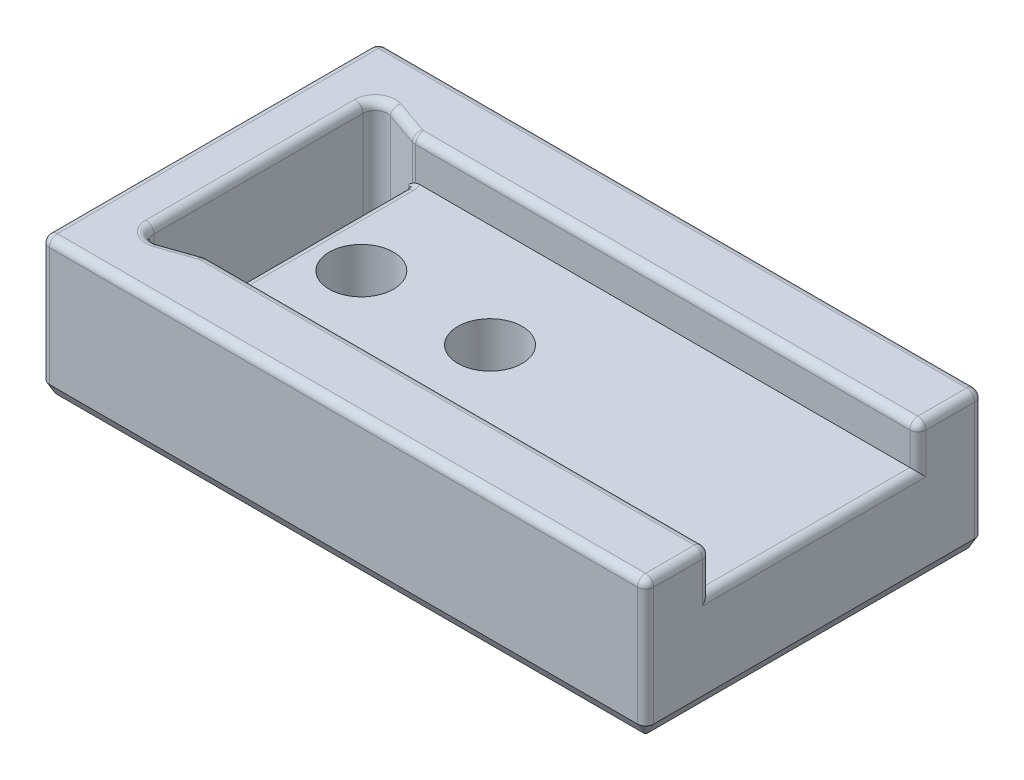
SolidWorks part; units mm, degrees
ref_plane "Front Plane" through (0, 0, 0) normal (0, 0, 1) x (1, 0, 0)
ref_plane "Top Plane" through (0, 0, 0) normal (0, 1, 0) x (1, 0, 0)
ref_plane "Right Plane" through (0, 0, 0) normal (1, 0, 0) x (0, 0, -1)
ref_axis "Axis X" through (-88.99, 0, 0) along (1, 0, 0)
ref_axis "Axis Y" through (0, 55, 0) along (0, -1, 0)
ref_axis "Axis Z" through (0, 0, -88.99) along (0, 0, 1)
sketch "Sketch1" plane through (0, 0, 0) normal (0, 1, 0) x (1, 0, 0)
  line L0 (3, 7.5) -> (3, -7.5)
  line L1 (0, -10.4) -> (37.2875, -10.4)
  line L2 (0, -10.4) -> (0, 10.4)
  line L3 (0, 10.4) -> (37.2875, 10.4)
  line L4 (37.2875, -10.4) -> (37.2875, 10.4)
  line L5 (6.175, -6.4) -> (37.2875, -6.4)
  line L6 (6.175, 6.4) -> (37.2875, 6.4)
  line L7 (-4.675, 0) -> (4.675, 0) construction
  line L8 (6.175, 6.4) -> (6.175, -6.4)
  line L9 (3, 7.5) -> (6.175, 6.4)
  line L10 (3, -7.5) -> (6.175, -6.4)
  point P4 (0, 0)
  point P8 (9.35, 0)
  point P11 (17.2875, 0)
  point P16 (3, 0)
  dimension "D1" = 12.8
  dimension "D2" = 20
  dimension "D3" = 7.9375
  dimension "D4" = 6.35
  dimension "D5" = 4
  dimension "D6" = 3
  dimension "D7" = 3.175
  dimension "D8" = 15
extrude "Boss-Extrude1" add sketch "Sketch1" along normal blind 2.5 contours L0 L6 L4 L3 L2 L1 L5 region at (2.573, 0, 0)
extrude "Boss-Extrude2" add sketch "Sketch1<3>" against normal blind 6 contours L6 L8 L5 L4 | L0 L6 L4 L3 L2 L1 L5 region at (2.573, 0, 0) region at (21.7313, 0, 0)
sketch "Sketch1<3>" plane through (0, 0, 0) normal (0, 1, 0) x (1, 0, 0) same geometry as "Sketch1"
fillet "Fillet1" radius 0.75 4 edges at (3, -1.75, 7.5) (6.175, -3, 6.4) (6.175, -3, -6.4) (3, -1.75, -7.5)
fillet "Fillet2" radius 0.75 2 edges at (6.175, 1.25, 6.4) (6.175, 1.25, -6.4)
fillet "Fillet3" radius 0.5 24 edges at (37.2875, 2.5, 8.4) (18.6438, 2.5, 10.4) (0, 2.5, 0) (18.6438, 2.5, -10.4) (37.2875, 2.5, -8.4) (21.7944, 2.5, -6.4) (6.1768, 2.5, -6.4104) (5.0256, 2.5, -6.7982) (3.3151, 2.5, -7.0574) (3, 2.5, 0) (3.3151, 2.5, 7.0574) (5.0256, 2.5, 6.7982) (6.1768, 2.5, 6.4104) (21.7944, 2.5, 6.4) (0, -1.75, -10.4) (0, -1.75, 10.4) (37.2875, -1.75, -10.4) (37.2875, -1.75, 10.4) (37.2875, 1.25, 6.4) (37.2875, 1.25, -6.4) (6.036, 0, -6.3011) (6.036, 0, 6.3011) (6.175, 0, 0) (37.2875, 0, 0)
hole_wizard "5/32 (0.15625) Diameter Hole1" positions "Sketch2" profile "Sketch3" hole size "5/32" standard "ANSI Inch" end condition up to next
sketch "Sketch2" plane through (0, 0, 0) normal (0, 1, 0) x (1, 0, 0)
  point P0 (9.35, 0)
  point P3 (17.2875, 0)
sketch "Sketch3" plane through (9.35, 0, 0) normal (1, 0, 0) x (0, 0, 1)
  line L0 (0, 0) -> (0, 6)
  line L1 (0, 6) -> (1.9844, 6)
  line L2 (1.9844, 6) -> (1.9844, 0)
  line L5 (1.9844, 0) -> (0, 0)
  line L11 (0, -6.35) -> (0, 107.95) construction
  dimension "Thru Hole Dia." = 3.9688
  dimension "Thru Hole Depth" = 6
chamfer "Chamfer1" distance 0.4 angle 60 18 edges at (6.036, -6, -6.3011) (6.175, -6, 0) (6.036, -6, 6.3011) (4.833, -6, 6.8649) (3.3151, -6, 7.0574) (3, -6, 0) (3.3151, -6, -7.0574) (4.833, -6, -6.8649) (0.1464, -6, 10.2536) (18.6438, -6, 10.4) (37.1411, -6, 10.2536) (37.2875, -6, 0) (37.1411, -6, -10.2536) (18.6438, -6, -10.4) (0.1464, -6, -10.2536) (0, -6, 0) (17.2875, -6, 1.9844) (9.35, -6, 1.9844) first distance on face at (5.9794, -3.25, -6.2607) first distance on face at (6.175, -3.25, 0) first distance on face at (5.9794, -3.25, 6.2607) first distance on face at (5.2727, -1.4238, 6.7126) first distance on face at (3.4064, -2, 6.9291) first distance on face at (3, -2, 0) first distance on face at (3.4064, -2, -6.9291) first distance on face at (5.2085, -1.4746, -6.7349) first distance on face at (9.35, -6, 1.9844)
equation "\"D7@Sketch1\"=\"D4@Sketch1\"/2"
